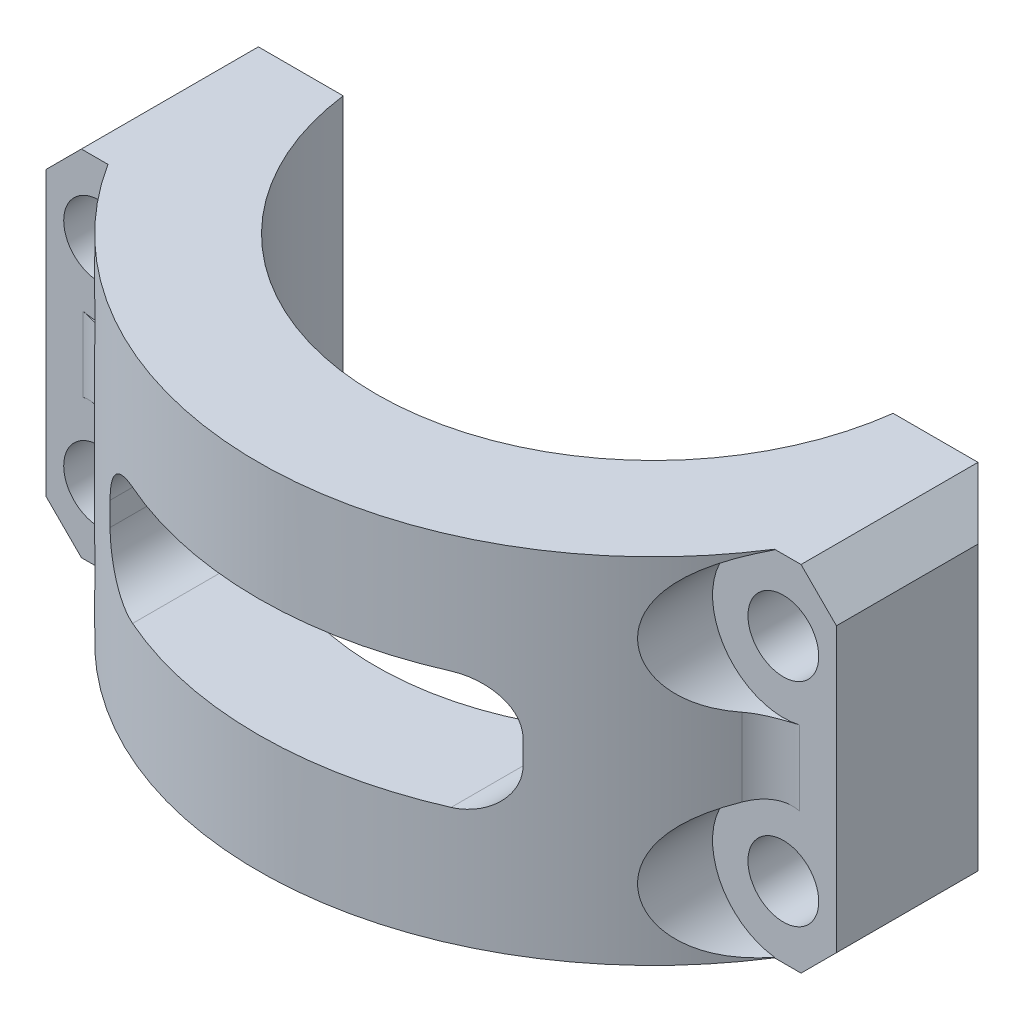
SolidWorks part; units mm, degrees
material "ABS"
ref_plane "Front Plane" through (0, 0, 0) normal (0, 0, 1) x (1, 0, 0)
ref_plane "Top Plane" through (0, 0, 0) normal (0, 1, 0) x (1, 0, 0)
ref_plane "Right Plane" through (0, 0, 0) normal (1, 0, 0) x (0, 0, -1)
sketch "Sketch1" plane through (0, 0, 0) normal (0, 1, 0) x (1, 0, 0)
  line L0 (0, 0) -> (23.5, 0) construction
  line L1 (23.3077, -3) -> (33.5, -3)
  line L2 (33.5, -3) -> (33.5, -18)
  line L3 (0, 0) -> (0, -16.3802) construction
  line L4 (33.5, -18) -> (28.2533, -18)
  line L5 (-33.5, -18) -> (-28.2533, -18)
  line L6 (-33.5, -3) -> (-33.5, -18)
  line L7 (-23.3077, -3) -> (-33.5, -3)
  circle A0 centre (0, 0) radius 23.5
  circle A1 centre (0, 0) radius 33.5
  dimension "D1" = 47
  dimension "D3" = 15
  dimension "D4" = 3
  dimension "D5" = 67
  dimension "D2" = 10
extrude "Boss-Extrude1" add sketch "Sketch1" along normal mid plane 30 contours A1 L7 L6 L5 | A1 L1 A0 L7 | A1 L4 L2 L1 region at (28.3366, 0, 3.7337) region at (31.9429, 0, 13.6238) region at (-31.9429, 0, 13.6238)
sketch "Sketch2" plane through (0, 0, 0) normal (0, 0, 1) x (1, 0, 0)
  line L0 (0, 0) -> (14.8135, 0) construction
  line L1 (0, 0) -> (0, -10.4047) construction
  circle A0 centre (29, -9) radius 3
  circle A1 centre (29, 9) radius 3
  circle A2 centre (-29, 9) radius 3
  circle A3 centre (-29, -9) radius 3
  dimension "D1" = 6
  dimension "D2" = 18
  dimension "D3" = 58
extrude "Cut-Extrude1" cut sketch "Sketch2" along normal blind 30
sketch "Sketch3" plane through (0, 0, 0) normal (0, 0, 1) x (1, 0, 0)
  line L1 (-17.5, 5) -> (17.5, 5)
  line L2 (-17.5, 5) -> (-17.5, -5)
  line L3 (-17.5, -5) -> (17.5, -5)
  line L4 (17.5, 5) -> (17.5, -5)
  line L5 (-17.5, 5) -> (17.5, -5) construction
  line L6 (-17.5, -5) -> (17.5, 5) construction
  point P0 (0, 0)
  dimension "D1" = 10
  dimension "D2" = 35
extrude "Cut-Extrude2" cut sketch "Sketch3" along normal through all
fillet "Fillet1" radius 4 4 edges at (17.5, -5, 22.1251) (17.5, 5, 22.1251) (-17.5, -5, 22.1251) (-17.5, 5, 22.1251)
sketch "Sketch4" plane through (0, 0, 18) normal (0, 0, 1) x (1, 0, 0)
  line L0 (0, 0) -> (0, 22.9027) construction
  line L1 (0, 0) -> (42.0379, 0) construction
  circle A0 centre (29, 9) radius 6
  circle A1 centre (29, -9) radius 6
  circle A2 centre (-29, -9) radius 6
  circle A3 centre (-29, 9) radius 6
  dimension "D1" = 12
extrude "Cut-Extrude3" cut sketch "Sketch4" along normal blind 30
fillet "Fillet2" radius 4 2 edges at (28.2533, 0, 18) (-28.2533, 0, 18)
chamfer "Chamfer1" distance 3 angle 45 6 edges at (33.5, 0, 3) (33.5, -15, 10.5) (33.5, 15, 10.5) (-33.5, 0, 3) (-33.5, 15, 10.5) (-33.5, -15, 10.5)
